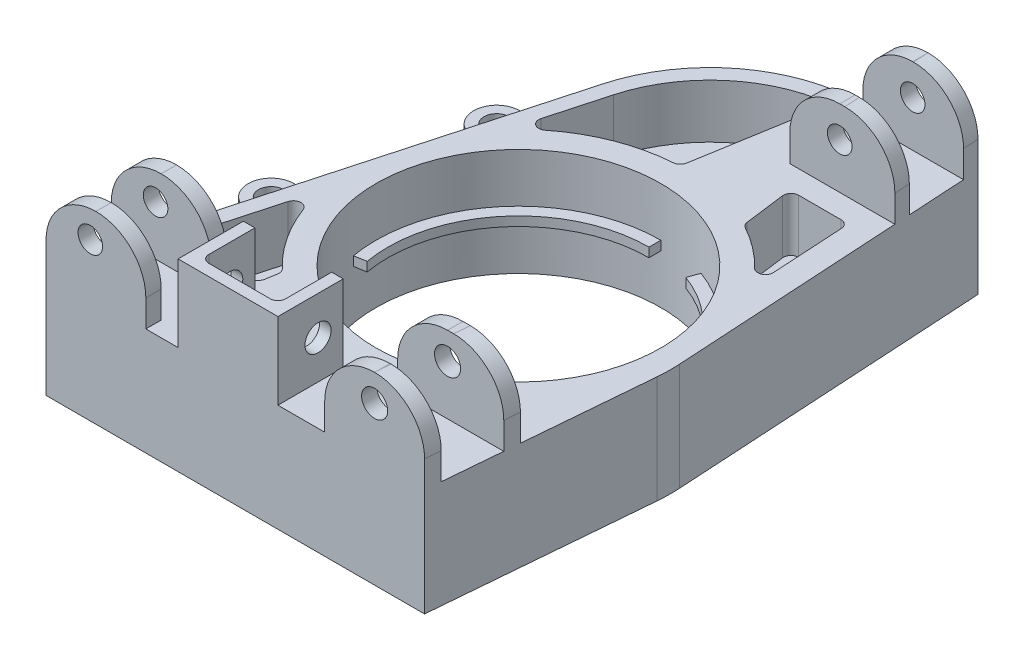
SolidWorks part; units mm, degrees
ref_plane "Front Plane" through (0, 0, 0) normal (0, 0, 1) x (1, 0, 0)
ref_plane "Top Plane" through (0, 0, 0) normal (0, 1, 0) x (1, 0, 0)
ref_plane "Right Plane" through (0, 0, 0) normal (1, 0, 0) x (0, 0, -1)
sketch "Sketch1" plane through (0, 0, 0) normal (0, 1, 0) x (1, 0, 0)
  line L0 (-76.5386, -79.7284) -> (48.6713, -79.7284)
  line L1 (55.0613, -5.2886) -> (48.6713, 103.3395)
  line L2 (48.6713, 103.3395) -> (10.8418, 103.3395)
  line L3 (-38.131, 66.0414) -> (-70.9669, -53.0584)
  line L4 (48.6713, 103.3395) -> (48.6713, -79.7284) construction
  line L5 (48.6713, -79.7284) -> (55.0613, -5.2886)
  line L6 (-76.5386, -79.7284) -> (-76.5386, -53.0584)
  line L7 (-76.5386, -53.0584) -> (-70.9669, -53.0584)
  circle A0 centre (0, 0) radius 47.117
  circle A2 centre (0, 0) radius 120.65
  arc A3 (10.8418, 103.3395) -> (-38.131, 66.0414) centre (10.8418, 52.5395) ccw
  point P10 (0, -47.117)
  point P11 (47.117, 0)
  point P16 (-47.117, 0)
  dimension "D2" = 94.234
  dimension "D3" = 7.62
  dimension "D4" = 8.89
  dimension "D5" = 26.67
  dimension "D1" = 241.3
  dimension "D6" = 50.8
extrude "Base" add sketch "Sketch1" along normal blind 35.56 contours L2 L3 L0 L1 A0 | L1 L4 A0 L5 region at (-74.284, 0, 66.3934)
sketch "Sketch2" plane through (0, 35.56, 0) normal (0, 1, 0) x (1, 0, 0)
  line L0 (48.6713, 103.3395) -> (48.9701, 98.2595)
  line L1 (55.0613, -5.2886) -> (48.6713, 103.3395) construction
  line L2 (48.9701, 98.2595) -> (15.6513, 98.2595)
  line L3 (15.6513, 98.2595) -> (15.6513, 103.3395)
  line L4 (48.6713, 103.3395) -> (10.8418, 103.3395) construction
  line L5 (15.6513, 103.3395) -> (48.6713, 103.3395)
  line L6 (15.6513, -74.6484) -> (49.1074, -74.6484)
  line L7 (49.1074, -74.6484) -> (48.6713, -79.7284)
  line L8 (-76.5386, -79.7284) -> (48.6713, -79.7284) construction
  line L9 (48.6713, -79.7284) -> (15.6513, -79.7284)
  line L10 (15.6513, -79.7284) -> (15.6513, -74.6484)
  line L11 (15.6513, 103.3395) -> (15.6513, -79.7284) construction
  line L12 (48.6713, -79.7284) -> (55.0613, -5.2886) construction
  line L13 (15.6513, 79.2095) -> (15.6513, 74.1295)
  line L14 (15.6513, 74.1295) -> (50.3896, 74.1295)
  line L15 (50.3896, 74.1295) -> (50.0907, 79.2095)
  line L16 (50.0907, 79.2095) -> (15.6513, 79.2095)
  line L17 (-76.5386, -79.7284) -> (-76.5386, -53.0584) construction
  line L18 (15.6513, -50.5184) -> (51.1787, -50.5184)
  line L19 (15.6513, -50.5184) -> (15.6513, -55.5984)
  line L20 (15.6513, -55.5984) -> (50.7427, -55.5984)
  line L21 (51.1787, -50.5184) -> (50.7427, -55.5984)
  line L22 (-43.5186, -53.0584) -> (-76.5386, -53.0584)
  line L23 (-43.5186, -53.0584) -> (-43.5186, -58.1384)
  line L24 (-43.5186, -58.1384) -> (-76.5386, -58.1384)
  line L25 (-76.5386, -53.0584) -> (-76.5386, -58.1384)
  line L26 (-43.5186, -79.7284) -> (-43.5186, -60.0458) construction
  line L27 (-76.5386, -74.6484) -> (-43.5186, -74.6484)
  line L28 (-76.5386, -74.6484) -> (-76.5386, -79.7284)
  line L29 (-76.5386, -79.7284) -> (-43.5186, -79.7284)
  line L30 (-43.5186, -74.6484) -> (-43.5186, -79.7284)
  line L31 (-76.5386, -79.7284) -> (48.6713, -79.7284) construction
  dimension "D1" = 33.02
  dimension "D2" = 5.08
  dimension "D3" = 5.08
  dimension "D4" = 19.05
  dimension "D5" = 5.08
  dimension "D6" = 5.08
  dimension "D7" = 19.05
  dimension "D8" = 33.02
  dimension "D9" = 5.08
  dimension "D10" = 5.08
extrude "A-Arms" add sketch "Sketch2" along normal blind 25.4
fillet "Fillet a-arm tab f" radius 16.51 12 edges at (48.8894, 60.96, 77.1884) (50.9607, 60.96, 53.0584) (15.6513, 60.96, 77.1884) (15.6513, 60.96, 53.0584) (50.2402, 60.96, -76.6695) (48.8207, 60.96, -100.7995) (15.6513, 60.96, -76.6695) (15.6513, 60.96, -100.7995) (-76.5386, 60.96, 77.1884) (-43.5186, 60.96, 77.1884) (-43.5186, 60.96, 55.5984) (-76.5386, 60.96, 55.5984)
fillet "Fillet2" radius 50.8 1 edges at (55.0613, 17.78, 5.2886)
ref_plane "Plane1" through (0, 16, 0) normal (0, -1, 0) x (-1, 0, 0)
sketch "Sketch3" plane through (0, 16, 0) normal (0, -1, 0) x (-1, 0, 0)
  line L0 (42.2021, 51.2753) -> (51.7371, 53.9041)
  line L1 (38.131, 66.0414) -> (70.9669, -53.0584) construction
  line L2 (62.3195, -21.6933) -> (72.1885, -18.9724)
  line L3 (54.0145, 33.5988) -> (63.3923, -0.4157)
  line L4 (42.2021, 51.2753) -> (62.3195, -21.6933)
  circle A0 centre (0, 0) radius 71.12
  circle A1 centre (53.7624, 46.5582) radius 4.191
  circle A2 centre (70.1632, -11.6265) radius 4.191
  arc A3 (56.852, 39.5926) -> (51.7371, 53.9041) centre (53.7624, 46.5582) ccw
  arc A4 (72.1885, -18.9724) -> (69.039, -4.0899) centre (70.1632, -11.6265) ccw
  arc A5 (63.3923, -0.4157) -> (69.039, -4.0899) centre (68.2896, 0.9345) ccw
  arc A6 (54.0145, 33.5988) -> (56.852, 39.5926) centre (58.9118, 34.949) cw
  dimension "D1" = 60.452
  dimension "D2" = 142.24
  dimension "D3" = 8.382
  dimension "D4" = 8.382
  dimension "D5" = 15.24
  dimension "D6" = 15.24
  dimension "D7" = 5.08
extrude "Boss-Extrude3" add sketch "Sketch3" against normal blind 10 contours L3 A6 A3 A0 A1 L0 L4 L2 A2 A4 A5 | A0 A3 L0 A1 | L2 A4 A0 A2 region at (-56.0903, 16, -15.5313) region at (-49.7533, 16, -53.1565) region at (-69.0083, 16, 17.9571)
fillet "Fillet3" radius 12.7 2 edges at (-42.2021, 21, -51.2753) (-62.3195, 21, 21.6933)
sketch "Sketch6" plane through (0, 0, -103.3395) normal (0, 0, -1) x (-1, 0, 0)
  line L0 (-32.1471, 60.96) -> (-32.1471, 40.2979) construction
  circle A1 centre (-32.1471, 50.673) radius 4.064
  dimension "D1" = 15.113
  dimension "D2" = 8.128
extrude "Tab Holes 1" cut sketch "Sketch6" against normal blind 38.1
sketch "Sketch7" plane through (0, 0, 53.0584) normal (0, 0, -1) x (-1, 0, 0)
  line L0 (60.0286, 60.96) -> (60.0286, 35.56) construction
  line L4 (43.5186, 35.56) -> (70.9669, 35.56) construction
  circle A0 centre (61.8814, 51.9657) radius 4.064
  dimension "D1" = 16.51
  dimension "D2" = 8.128
extrude "Tab Holes 2" cut sketch "Sketch7" against normal through all
ref_plane "midplane" through (0, 17.78, 0) normal (0, 1, 0) x (1, 0, 0)
sketch "Sketch8" plane through (0, 17.78, 0) normal (0, 1, 0) x (1, 0, 0)
  line L0 (0, 0) -> (0, 47.117)
  line L1 (0, 0) -> (16.115, 44.2755)
  line L2 (0, 0) -> (30.2862, -36.0937)
  line L3 (0, 0) -> (40.8045, -23.5585)
  line L4 (0, 0) -> (-46.4012, -8.1818)
  line L5 (0, 0) -> (-40.8045, -23.5585)
  circle A0 centre (0, 0) radius 47.117
  circle A1 centre (0, 0) radius 43.18
  circle A2 centre (0, 0) radius 47.117 construction
  point P14 (0, 0)
  dimension "D1" = 20
  dimension "D2" = 3
extrude "mid-feature bearing" add sketch "Sketch8" along normal blind 1.524 and the other way blind 1.524 contours A1 L0 A0 L4 | A1 L5 A0 L2 | A1 L3 A0 L1 region at (-33.6343, 17.78, -28.2226) region at (16.1479, 17.78, -42.1687) region at (28.4423, 17.78, 35.0713)
sketch "Sketch9" plane through (0, 35.56, 0) normal (0, 1, 0) x (1, 0, 0)
  line L0 (-43.5186, -79.7284) -> (15.6513, -79.7284) construction
  line L1 (-32.844, -79.7284) -> (0.176, -79.7284)
  line L2 (-32.844, -79.7284) -> (-32.844, -75.9184)
  line L3 (-32.844, -75.9184) -> (0.176, -75.9184)
  line L4 (0.176, -79.7284) -> (0.176, -75.9184)
  line L5 (-43.5186, -58.1384) -> (15.6513, -58.1384) construction
  line L6 (0.176, -75.9184) -> (-3.634, -75.9184)
  line L7 (0.176, -75.9184) -> (0.176, -58.1384)
  line L8 (0.176, -58.1384) -> (-3.634, -58.1384)
  line L9 (-3.634, -75.9184) -> (-3.634, -58.1384)
  line L10 (-32.844, -75.9184) -> (-29.034, -75.9184)
  line L11 (-32.844, -75.9184) -> (-32.844, -58.1384)
  line L12 (-32.844, -58.1384) -> (-29.034, -58.1384)
  line L13 (-29.034, -75.9184) -> (-29.034, -58.1384)
  line L14 (15.6513, -50.5184) -> (15.6513, -55.5984) construction
  line M30 (-43.5186, -79.7284) -> (15.6513, -79.7284)
  dimension "D1" = 3.81
  dimension "D2" = 3.81
  dimension "D3" = 3.81
  dimension "D4" = 25.4
extrude "Boss-Extrude5" add sketch "Sketch9" along normal blind 25.4 contours L3 L13 L12 L11 | L4 L3 L2 M30 | L9 L3 L7 L8 region at (-16.334, 35.56, 77.8234) region at (-30.939, 35.56, 67.0284) region at (-1.729, 35.56, 67.0284)
fillet "Pushrod Str" radius 2.54 2 edges at (-3.634, 48.26, 75.9184) (-29.034, 48.26, 75.9184)
sketch "Sketch10" plane through (-32.844, 0, 0) normal (-1, 0, 0) x (0, 0, 1)
  line L0 (58.1384, 48.26) -> (80.5175, 48.26) construction
  line L1 (58.1384, 60.96) -> (58.1384, 35.56) construction
  circle A0 centre (66.4613, 48.26) radius 4.318
  dimension "D1" = 8.3229
extrude "Pushrod Holes" cut sketch "Sketch10" against normal through all
mirror "Mirror2" [suppressed] of bodies 108
delete or keep bodies "Body-Delete/Keep 1" [suppressed] type delete bodies bodies 108
sketch "Sketch11" plane through (0, 0, 79.7284) normal (0, 0, -1) x (-1, 0, 0)
  line L0 (-32.1613, 60.96) -> (-32.1613, 35.56) construction
  line L2 (-15.6513, 35.56) -> (-48.6713, 35.56) construction
  line L3 (-48.6713, 44.45) -> (-48.6713, 0) construction
  circle A0 centre (-32.1613, 52.07) radius 4.318
  arc A1 (-15.6513, 44.45) -> (-32.131, 60.96) centre (-32.1613, 44.45) ccw construction
  dimension "D1" = 16.51
extrude "Tab Holes 3" cut sketch "Sketch11" along normal blind 50.8
ref_plane "Plane2" through (0, 0, -88.7345) normal (0, 0, -1) x (-1, 0, 0)
ref_axis "Axis1" through (32.1471, 50.673, -74.1295) along (0, 0, -1)
ref_point "top wishbont att pt"
ref_plane "Plane3" through (0, 0, 65.1234) normal (0, 0, -1) x (-1, 0, 0)
ref_axis "Axis2" through (32.1613, 52.07, 50.5184) along (0, 0, 1)
ref_point "Bottom Wish"
ref_axis "Axis3" through (-61.8814, 51.9657, 58.1384) along (0, 0, -1)
ref_point "Anchor tierod"
sketch "Sketch12" plane through (0, 35.56, 0) normal (0, 1, 0) x (1, 0, 0)
  line L0 (23.2751, 66.5392) -> (42.5844, 66.5392)
  line L1 (42.5844, 66.5392) -> (44.5791, 32.63)
  line L75 (5.2782, 97.9198) -> (-1.916, 55.2118)
  line L76 (22.9504, 69.0495) -> (25.5453, 48.9841)
  line L77 (-38.4386, -47.9784) -> (-37.2318, -40.8143)
  line L106 (-23.954, -70.8384) -> (-8.714, -70.8384)
  line L107 (-8.714, -70.8384) -> (-8.714, -53.0584)
  line L108 (-8.714, -53.0584) -> (5.256, -53.0584)
  line L109 (5.256, -53.0584) -> (5.256, -74.6484)
  line L110 (5.256, -74.6484) -> (10.5713, -74.6484)
  line L111 (10.5713, -74.6484) -> (10.5713, -69.5684)
  line L112 (10.5713, -69.5684) -> (44.4448, -69.5684)
  line L113 (44.4448, -69.5684) -> (45.2079, -60.6784)
  line L114 (45.2079, -60.6784) -> (10.5713, -60.6784)
  line L115 (10.5713, -60.6784) -> (10.5713, -45.4384)
  line L116 (10.5713, -45.4384) -> (46.5161, -45.4384)
  line L117 (46.5161, -45.4384) -> (49.6857, -8.5145)
  line L118 (49.7743, -1.9195) -> (45.5996, 69.0495)
  line L119 (45.5996, 69.0495) -> (10.5713, 69.0495)
  line L120 (10.5713, 69.0495) -> (10.5713, 84.2895)
  line L121 (10.5713, 84.2895) -> (44.7031, 84.2895)
  line L122 (44.7031, 84.2895) -> (44.1802, 93.1795)
  line L123 (44.1802, 93.1795) -> (10.5713, 93.1795)
  line L124 (10.5713, 93.1795) -> (10.5713, 98.2587)
  line L126 (-33.2338, 64.6912) -> (-64.2968, -47.9784)
  line L127 (-64.2968, -47.9784) -> (-38.4386, -47.9784)
  line L128 (-38.4386, -47.9784) -> (-38.4386, -63.2184)
  line L129 (-38.4386, -63.2184) -> (-71.4586, -63.2184)
  line L130 (-71.4586, -63.2184) -> (-71.4586, -69.5684)
  line L131 (-71.4586, -69.5684) -> (-38.4386, -69.5684)
  line L132 (-38.4386, -69.5684) -> (-38.4386, -74.6484)
  line L133 (-38.4386, -74.6484) -> (-37.924, -74.6484)
  line L134 (-37.924, -74.6484) -> (-37.924, -53.0584)
  line L135 (-37.924, -53.0584) -> (-23.954, -53.0584)
  line L136 (-23.954, -53.0584) -> (-23.954, -70.8384)
  line L137 (-23.954, -70.8384) -> (-8.714, -70.8384)
  line L138 (-8.714, -70.8384) -> (-8.714, -53.0584)
  line L139 (-8.714, -53.0584) -> (5.256, -53.0584)
  line L140 (5.256, -53.0584) -> (5.256, -74.6484)
  line L141 (5.256, -74.6484) -> (10.5713, -74.6484)
  line L142 (10.5713, -74.6484) -> (10.5713, -69.5684)
  line L143 (10.5713, -69.5684) -> (44.4448, -69.5684)
  line L144 (44.4448, -69.5684) -> (45.2079, -60.6784)
  line L145 (45.2079, -60.6784) -> (10.5713, -60.6784)
  line L146 (10.5713, -60.6784) -> (10.5713, -45.4384)
  line L147 (10.5713, -45.4384) -> (46.5161, -45.4384)
  line L148 (46.5161, -45.4384) -> (49.6857, -8.5145)
  line L149 (49.7743, -1.9195) -> (45.5996, 69.0495)
  line L150 (45.5996, 69.0495) -> (10.5713, 69.0495)
  line L151 (10.5713, 69.0495) -> (10.5713, 84.2895)
  line L152 (10.5713, 84.2895) -> (44.7031, 84.2895)
  line L153 (44.7031, 84.2895) -> (44.1802, 93.1795)
  line L154 (44.1802, 93.1795) -> (10.5713, 93.1795)
  line L155 (10.5713, 93.1795) -> (10.5713, 98.2587)
  line L157 (-33.2338, 64.6912) -> (-64.2968, -47.9784)
  line L158 (-64.2968, -47.9784) -> (-38.4386, -47.9784)
  line L159 (-38.4386, -47.9784) -> (-38.4386, -63.2184)
  line L160 (-38.4386, -63.2184) -> (-71.4586, -63.2184)
  line L161 (-71.4586, -63.2184) -> (-71.4586, -69.5684)
  line L162 (-71.4586, -69.5684) -> (-38.4386, -69.5684)
  line L163 (-38.4386, -69.5684) -> (-38.4386, -74.6484)
  line L164 (-38.4386, -74.6484) -> (-37.924, -74.6484)
  line L165 (-37.924, -74.6484) -> (-37.924, -53.0584)
  line L166 (-37.924, -53.0584) -> (-23.954, -53.0584)
  line L167 (-23.954, -53.0584) -> (-23.954, -70.8384)
  circle A22 centre (0, 0) radius 55.245
  arc A23 (49.6857, -8.5145) -> (49.7743, -1.9195) centre (4.1332, -4.6043) ccw
  arc A24 (10.5713, 98.2587) -> (-33.2338, 64.6912) centre (10.8418, 52.5395) ccw
  arc A25 (49.6857, -8.5145) -> (49.7743, -1.9195) centre (4.1332, -4.6043) ccw
  arc A26 (10.5713, 98.2587) -> (-33.2338, 64.6912) centre (10.8418, 52.5395) ccw
  dimension "D1" = 5.08
extrude "Cut-Extrude1" cut sketch "Sketch12" against normal blind 17.78 contours L75 A26 L157 A22 | A22 L1 L0 L76 | A22 L157 L158 L77 region at (35.0191, 35.56, -54.0623) region at (-15.4943, 35.56, -70.0275) region at (-51.5653, 35.56, 36.4569)
fillet "Fillet4" radius 2.54 11 edges at (-37.2318, 26.67, 40.8143) (-38.4386, 26.67, 47.9784) (-64.2968, 26.67, 47.9784) (-54.1231, 26.67, 11.077) (-40.8, 26.67, -37.2474) (5.2782, 26.67, -97.9198) (-1.916, 26.67, -55.2118) (25.5453, 26.67, -48.9841) (44.5791, 26.67, -32.63) (42.5844, 26.67, -66.5392) (23.2751, 26.67, -66.5392)
mirror "Mirror3" [suppressed] of bodies 112
delete or keep bodies "Body-Delete/Keep 2" [suppressed] type delete bodies bodies 112
